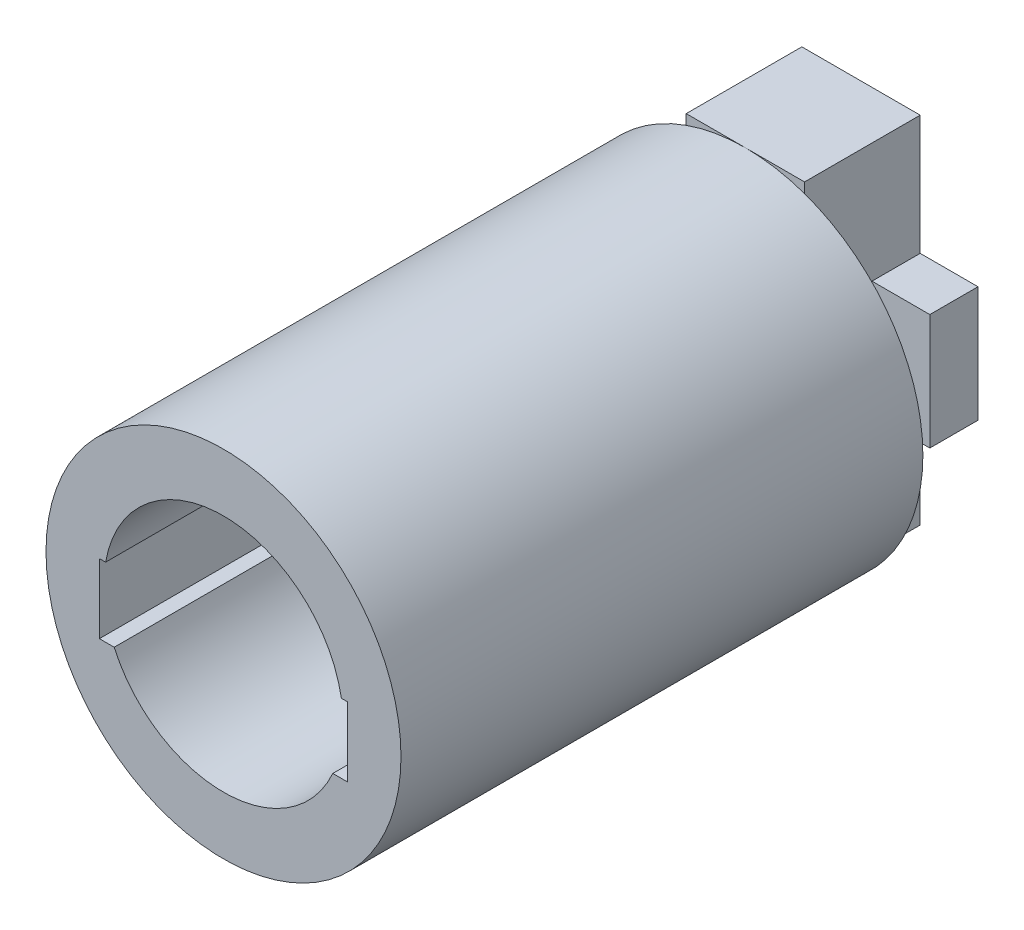
SolidWorks part; units mm, degrees
ref_plane "Front Plane" through (0, 0, 0) normal (0, 0, 1) x (1, 0, 0)
ref_plane "Top Plane" through (0, 0, 0) normal (0, 1, 0) x (1, 0, 0)
ref_plane "Right Plane" through (0, 0, 0) normal (1, 0, 0) x (0, 0, -1)
ref_plane "Plane6" through (0, 0, 0) normal (0, 0, 1) x (1, 0, 0)
sketch "Sketch9" plane through (0, 0, 0) normal (0, 0, 1) x (1, 0, 0)
  line L1 (21.1323, -4.604) -> (14.6923, -4.604) construction
  line L5 (14.6923, -3.704) -> (21.1323, -3.704)
  line L6 (14.6923, -3.704) -> (14.6923, -5.504)
  line L7 (14.6923, -5.504) -> (21.1323, -5.504)
  line L8 (21.1323, -3.704) -> (21.1323, -5.504)
  line L10 (17.9123, -5.504) -> (17.9123, -3.704) construction
  circle A0 centre (17.9123, -4.239) radius 4.605
  circle A1 centre (17.9123, -4.239) radius 3.105
  point P4 (0, 0)
  point P5 (0, 0)
  point P6 (0, 0)
  point P7 (0, 0)
  point P8 (0, 0)
  point P9 (17.9123, -4.604)
  dimension "D1" = 6.21
  dimension "D8" = 1.5
  dimension "D3" = 0.9
  dimension "D4" = 0.9
  dimension "D6" = 3.22
  dimension "D7" = 3.22
ref_plane "Plane8" through (0, 0, -13.54) normal (0, 0, 1) x (1, 0, 0)
extrude "Boss-Extrude6" add sketch "Sketch9" against normal up to surface (13.54 mm away) contours A0 A1 L5 L8 L7 L6 region at (13.4375, -4.239, 0) up to plane "Plane8"
sketch "Sketch11" plane through (0, 0, -13.54) normal (0, 0, 1) x (1, 0, 0)
  line L1 (16.3773, -8.844) -> (19.4473, -8.844)
  line L2 (16.3773, -8.844) -> (16.3773, 0.366)
  line L3 (16.3773, 0.366) -> (19.4473, 0.366)
  line L4 (19.4473, -8.844) -> (19.4473, 0.366)
  line L5 (16.3773, -8.844) -> (19.4473, 0.366) construction
  line L6 (16.3773, 0.366) -> (19.4473, -8.844) construction
  line L8 (14.8773, -5.739) -> (20.9473, -5.739)
  line L9 (14.8773, -5.739) -> (14.8773, -2.739)
  line L10 (14.8773, -2.739) -> (20.9473, -2.739)
  line L11 (20.9473, -5.739) -> (20.9473, -2.739)
  line L12 (14.8773, -5.739) -> (20.9473, -2.739) construction
  line L13 (14.8773, -2.739) -> (20.9473, -5.739) construction
  point P0 (17.9123, -4.239)
  point P8 (0, 0)
  point P9 (17.9123, -4.239)
  point P14 (0, 0)
  dimension "D1" = 3.07
  dimension "D2" = 3
  dimension "D3" = 1.5
extrude "Boss-Extrude7" add sketch "Sketch11" against normal blind 3 contours L2 L3 L4 L1
ref_plane "Plane9" through (0, 0, -16.54) normal (0, 0, -1) x (-1, 0, 0)
extrude "Boss-Extrude8" add sketch "Sketch11<7>" along normal blind 1.25 from surface contours L8 L11 L10 L4 | L10 L9 L8 L2 region at (15.6273, -4.239, -13.54) region at (20.1973, -4.239, -13.54) starting at plane "Plane9"
sketch "Sketch11<7>" plane through (0, 0, -13.54) normal (0, 0, 1) x (1, 0, 0) same geometry as "Sketch11"
equation "\"D1@Boss-Extrude8\"=1.50mm-.25"
